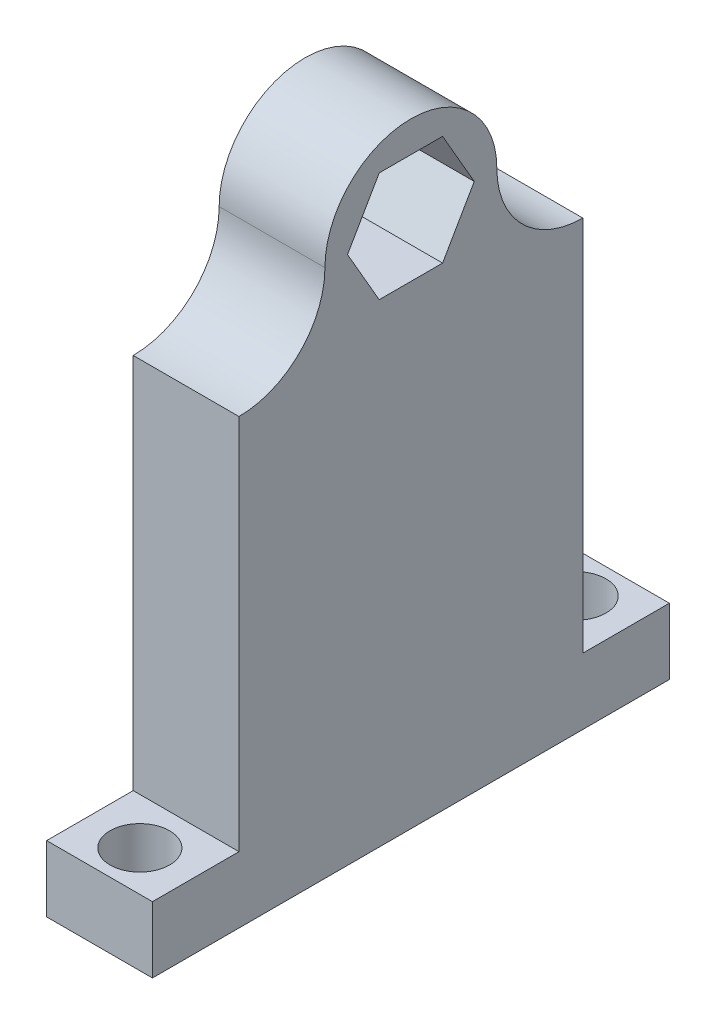
SolidWorks part; units mm, degrees
ref_plane "Спереди" through (0, 0, 0) normal (0, 0, 1) x (1, 0, 0)
ref_plane "Сверху" through (0, 0, 0) normal (0, 1, 0) x (1, 0, 0)
ref_plane "Справа" through (0, 0, 0) normal (1, 0, 0) x (0, 0, -1)
sketch "Эскиз1" plane through (0, 0, 0) normal (1, 0, 0) x (0, 0, -1)
  line L6 (-6.5, 0) -> (6.5, 0) construction
  line L12 (-13, -6.5) -> (-13, -11.5)
  line L13 (13, -6.5) -> (13, -11.5)
  line L15 (-13, -11.5) -> (13, -11.5)
  arc A0 (6.5, 0) -> (-6.5, 0) centre (0, 0) ccw
  arc A1 (-13, -6.5) -> (-6.5, 0) centre (-13, 0) ccw
  arc A2 (6.5, 0) -> (13, -6.5) centre (13, 0) ccw
  point P4 (0, 0)
  point P7 (0, -39.795)
  point P9 (0, 6.5)
  dimension "D1" = 13
  dimension "D4" = 13
  dimension "D5" = 13
  dimension "D2" = 5
extrude "Бобышка-Вытянуть1" add sketch "Эскиз1" along normal blind 8
sketch "Эскиз2" plane through (8, 0, 0) normal (1, 0, 0) x (0, 0, -1)
  line L1 (4.792, 0) -> (2.396, 4.15)
  line L2 (2.396, 4.15) -> (-2.396, 4.15)
  line L3 (-2.396, 4.15) -> (-4.792, 0)
  line L4 (-4.792, 0) -> (-2.396, -4.15)
  line L5 (-2.396, -4.15) -> (2.396, -4.15)
  line L6 (2.396, -4.15) -> (4.792, 0)
  circle A0 centre (0, 0) radius 4.15 construction
  dimension "D1" = 8.3
extrude "Вырез-Вытянуть1" cut sketch "Эскиз2" against normal through all
sketch "Эскиз4" plane through (0, -11.5, 0) normal (0, -1, 0) x (1, 0, 0)
  line L8 (0, 13) -> (0, -13)
  line L9 (0, -13) -> (8, -13)
  line L10 (8, -13) -> (8, 13)
  line L11 (8, 13) -> (0, 13)
  line L12 (0, 13) -> (0, -13)
  line L13 (0, -13) -> (8, -13)
  line L14 (8, -13) -> (8, 13)
  line L15 (8, 13) -> (0, 13)
  dimension "D1" = 0
extrude "Бобышка-Вытянуть2" add sketch "Эскиз4" along normal up to surface (28.5 mm away)
sketch "Эскиз5" plane through (0, -40, 0) normal (0, -1, 0) x (1, 0, 0)
  line L0 (0, 13) -> (0, -13) construction
  line L1 (0, 19.5455) -> (8, 19.5455)
  line L2 (0, 19.5455) -> (0, -19.5455)
  line L3 (0, -19.5455) -> (8, -19.5455)
  line L4 (8, 19.5455) -> (8, -19.5455)
  line L5 (8, -13) -> (8, 13) construction
  line L6 (533.9999, -19.5455) -> (-6.0001, -19.5455) construction
  line L7 (533.9999, 19.5455) -> (-6.0001, 19.5455) construction
  line L8 (4, -16.5) -> (4, 16.5) construction
  line L9 (8, -19.5455) -> (0, 19.5455) construction
  line L10 (0, -19.5455) -> (8, 19.5455) construction
  circle A0 centre (4, -16.5) radius 2.25
  circle A1 centre (4, 16.5) radius 2.25
  point P16 (4, 0)
  point P17 (8, 0)
  point P18 (4, 0)
  dimension "D1" = 4.5
  dimension "D2" = 4.5
  dimension "D3" = 33
extrude "Бобышка-Вытянуть3" add sketch "Эскиз5" against normal blind 5
